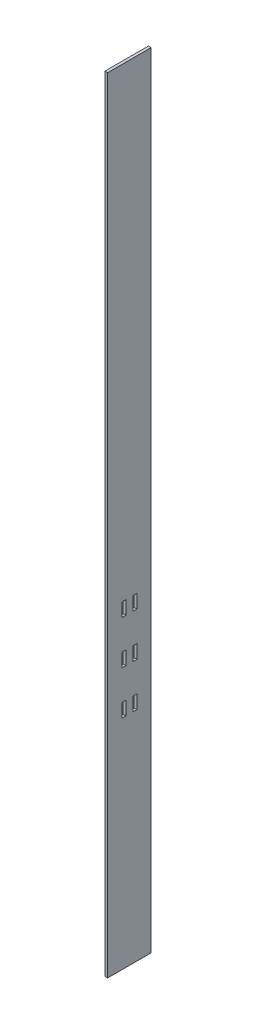
SolidWorks part; units mm, degrees
ref_plane "Front Plane" through (0, 0, 0) normal (0, 0, 1) x (1, 0, 0)
ref_plane "Top Plane" through (0, 0, 0) normal (0, 1, 0) x (1, 0, 0)
ref_plane "Right Plane" through (0, 0, 0) normal (1, 0, 0) x (0, 0, -1)
sketch "Sketch1" plane through (0, 0, 0) normal (1, 0, 0) x (0, 0, -1)
  line L1 (-25.4, 457.2) -> (25.4, 457.2)
  line L2 (-25.4, 457.2) -> (-25.4, -457.2)
  line L3 (-25.4, -457.2) -> (25.4, -457.2)
  line L4 (25.4, 457.2) -> (25.4, -457.2)
  line L5 (-25.4, 457.2) -> (25.4, -457.2) construction
  line L6 (-25.4, -457.2) -> (25.4, 457.2) construction
  point P0 (0, 0)
  dimension "D1" = 914.4
  dimension "D2" = 50.8
extrude "Boss-Extrude1" add sketch "Sketch1" along normal blind 3.175
sketch "Sketch2" plane through (3.175, 0, 0) normal (1, 0, 0) x (0, 0, -1)
  line L0 (-25.4, -457.2) -> (25.4, -457.2) construction
  line L1 (4, -136.525) -> (8.7625, -136.525)
  line L2 (4, -136.525) -> (4, -152.4)
  line L3 (4, -152.4) -> (8.7625, -152.4)
  line L4 (8.7625, -136.525) -> (8.7625, -152.4)
  line L5 (4, -136.525) -> (8.7625, -152.4) construction
  line L6 (4, -152.4) -> (8.7625, -136.525) construction
  point P0 (6.3813, -144.4625)
  dimension "D1" = 4.7625
  dimension "D2" = 15.875
  dimension "D3" = 304.8
  dimension "D4" = 4
extrude "Cut-Extrude1" cut sketch "Sketch2" against normal through all
mirror "Mirror1" about plane through (0, 0, 0) normal (0, 0, 1) of "Cut-Extrude1"
pattern_linear "LPattern1" count 2 spacing 50.8 along (0, 1, 0) count 2 spacing 50.8 along (0, -1, 0) of "Mirror1"
